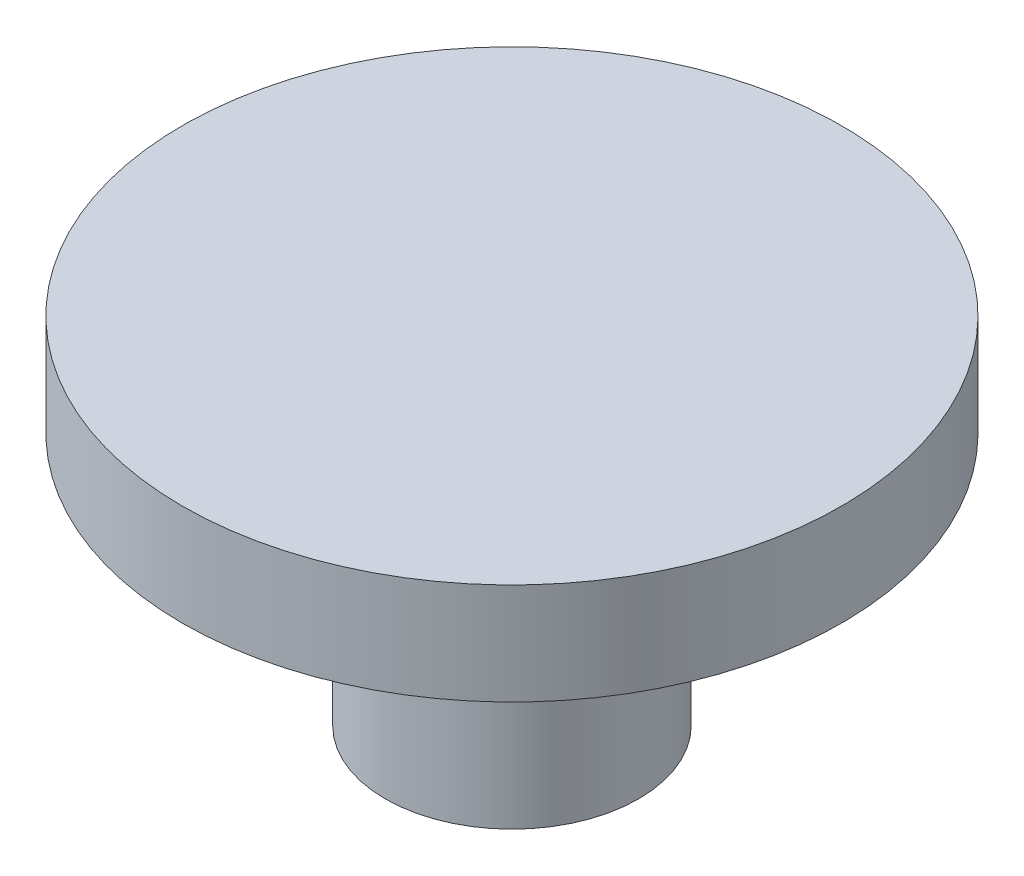
SolidWorks part; units mm, degrees
ref_plane "Front Plane" through (0, 0, 0) normal (0, 0, 1) x (1, 0, 0)
ref_plane "Top Plane" through (0, 0, 0) normal (0, 1, 0) x (1, 0, 0)
ref_plane "Right Plane" through (0, 0, 0) normal (1, 0, 0) x (0, 0, -1)
sketch "Sketch1" plane through (0, 0, 0) normal (0, 1, 0) x (1, 0, 0)
  circle A0 centre (0, 0) radius 19.5
  dimension "D1" = 39
extrude "Boss-Extrude1" add sketch "Sketch1" along normal blind 6
sketch "Sketch2" plane through (0, 0, 0) normal (0, -1, 0) x (1, 0, 0)
  circle A0 centre (0, 0) radius 7.5
  circle A1 centre (0, 0) radius 2.1
  dimension "D1" = 15
  dimension "D2" = 4.2
extrude "Boss-Extrude2" add sketch "Sketch2" along normal blind 15
